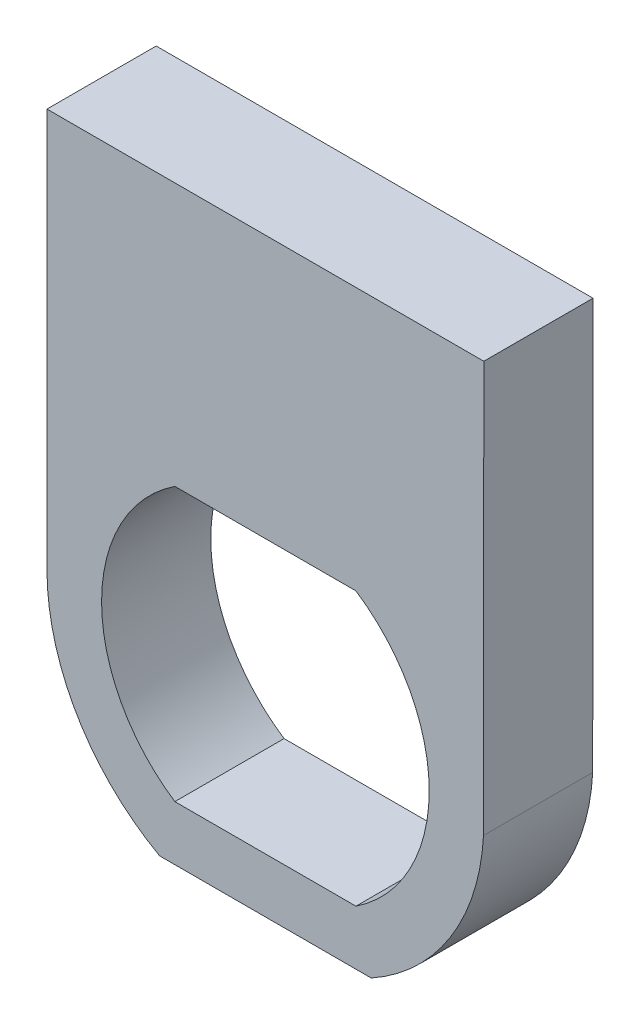
SolidWorks part; units mm, degrees
ref_plane "Front Plane" through (0, 0, 0) normal (0, 0, 1) x (1, 0, 0)
ref_plane "Top Plane" through (0, 0, 0) normal (0, 1, 0) x (1, 0, 0)
ref_plane "Right Plane" through (0, 0, 0) normal (1, 0, 0) x (0, 0, -1)
sketch "Sketch1" plane through (0, 0, 0) normal (0, 0, 1) x (1, 0, 0)
  line L0 (3.873, -7) -> (-3.873, -7)
  line L1 (3.3166, -5) -> (-3.3166, -5)
  line L2 (3.3166, 5) -> (-3.3166, 5)
  line L4 (-8, 0) -> (-8, 14.6269)
  line L5 (-8, 14.6269) -> (8, 14.6269)
  line L6 (8, 14.6269) -> (7.9889, -0.4209)
  line L9 (3.873, 7) -> (-3.873, 7) construction
  circle A0 centre (0, 0) radius 10 construction
  arc A1 (3.3166, -5) -> (3.3166, 5) centre (0, 0) ccw
  arc A2 (-3.3166, 5) -> (-3.3166, -5) centre (0, 0) ccw
  arc A3 (-8, 0) -> (-3.873, -7) centre (0, 0) ccw
  arc A4 (3.873, -7) -> (7.9895, 0.4091) centre (0, 0) ccw
  arc A6 (-3.873, 7) -> (-3.873, -7) centre (0, 0) ccw construction
  arc A7 (3.873, -7) -> (3.873, 7) centre (0, 0) ccw construction
  dimension "D1" = 20
  dimension "D3" = 12
  dimension "D2" = 5
  dimension "D4" = 5
  dimension "D5" = 2
extrude "Boss-Extrude1" add sketch "Sketch1" along normal blind 4 contours L0 A4 L6 L5 L4 A3 A2 L2 A1 L1 region at (-0.0029, 6.2561, 0)
